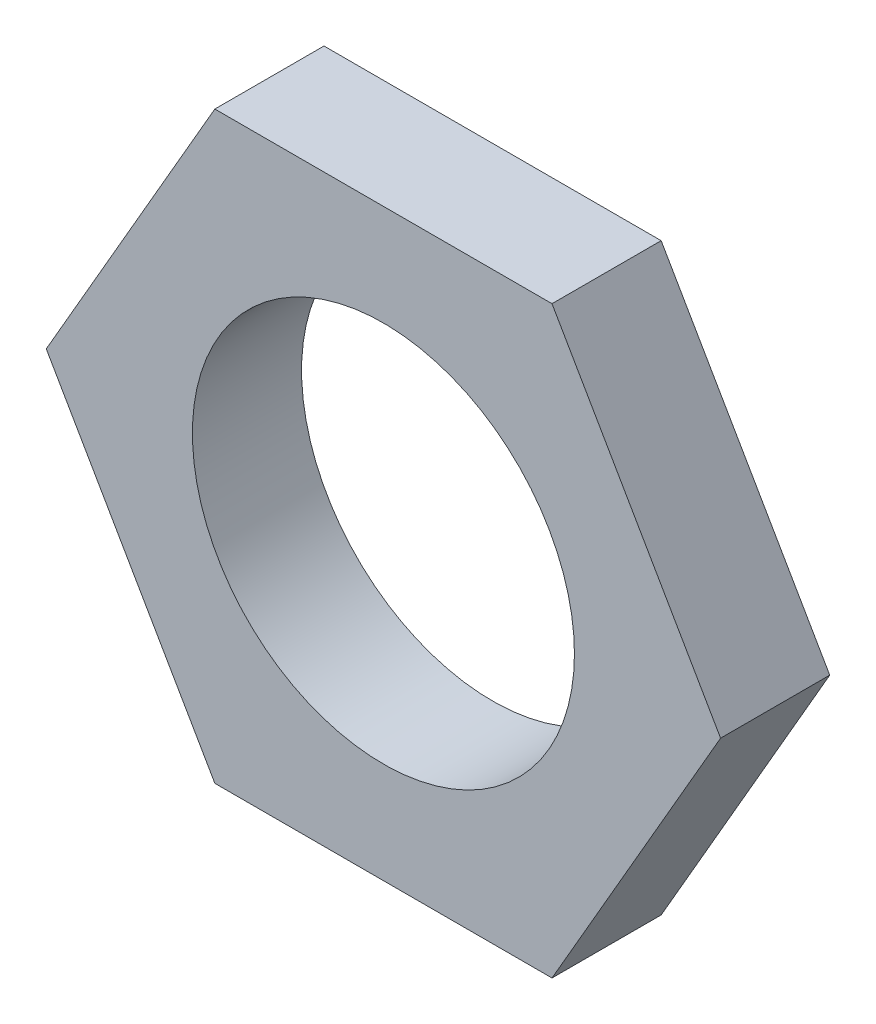
SolidWorks part; units mm, degrees
ref_plane "Front Plane" through (0, 0, 0) normal (0, 0, 1) x (1, 0, 0)
ref_plane "Top Plane" through (0, 0, 0) normal (0, 1, 0) x (1, 0, 0)
ref_plane "Right Plane" through (0, 0, 0) normal (1, 0, 0) x (0, 0, -1)
sketch "Sketch1" plane through (0, 0, 0) normal (0, 0, 1) x (1, 0, 0)
  line L1 (-6.1776, 0) -> (-3.0888, -5.35)
  line L2 (-3.0888, -5.35) -> (3.0888, -5.35)
  line L3 (3.0888, -5.35) -> (6.1776, 0)
  line L4 (6.1776, 0) -> (3.0888, 5.35)
  line L5 (3.0888, 5.35) -> (-3.0888, 5.35)
  line L6 (-3.0888, 5.35) -> (-6.1776, 0)
  circle A0 centre (0, 0) radius 5.35 construction
  dimension "D1" = 10.7
  dimension "D2" = 5.35
extrude "Boss-Extrude1" add sketch "Sketch1" along normal blind 2
sketch "Sketch2" plane through (0, 0, 2) normal (0, 0, 1) x (1, 0, 0)
  circle A0 centre (0, 0) radius 3.5
  dimension "D1" = 7
extrude "Cut-Extrude1" cut sketch "Sketch2" against normal blind 2
